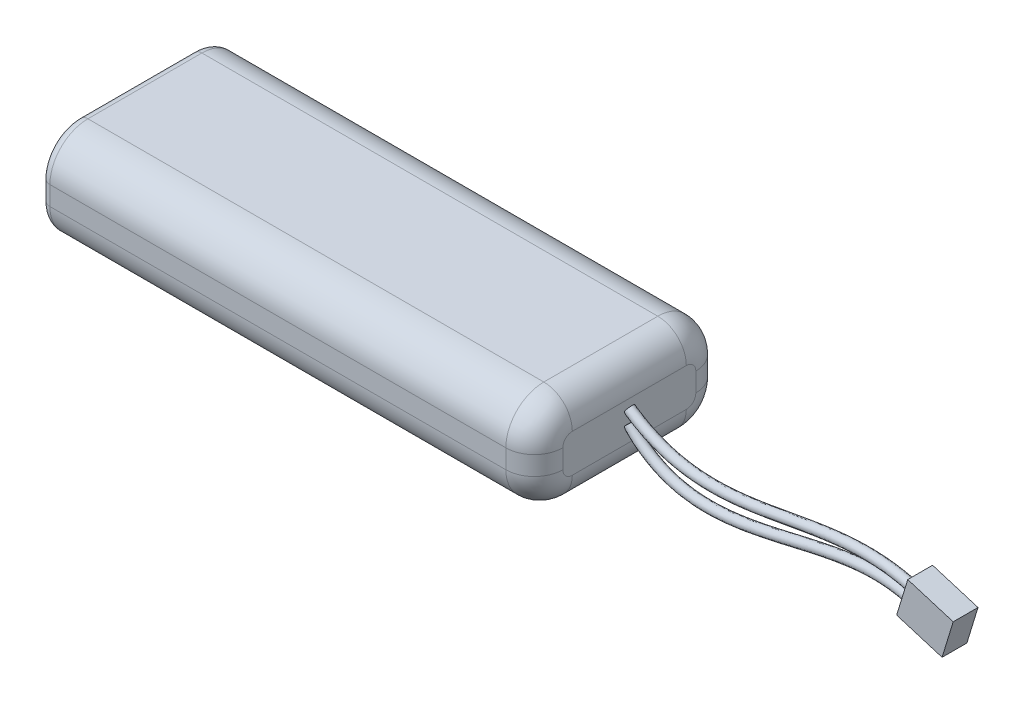
SolidWorks part; units mm, degrees
ref_plane "Front Plane" through (0, 0, 0) normal (0, 0, 1) x (1, 0, 0)
ref_plane "Top Plane" through (0, 0, 0) normal (0, 1, 0) x (1, 0, 0)
ref_plane "Right Plane" through (0, 0, 0) normal (1, 0, 0) x (0, 0, -1)
sketch "Sketch1" plane through (0, 0, 0) normal (0, 0, 1) x (1, 0, 0)
  line L1 (0, 0) -> (52, 0)
  line L2 (0, 0) -> (0, 10)
  line L3 (0, 10) -> (52, 10)
  line L4 (52, 0) -> (52, 10)
  dimension "D1" = 52
  dimension "D2" = 10
extrude "Boss-Extrude1" add sketch "Sketch1" along normal blind 20
fillet "Fillet2" radius 4 4 edges at (26, 0, 0) (26, 10, 0) (26, 0, 20) (26, 10, 20)
fillet "Fillet3" radius 3 8 edges at (52, 1.1716, 18.8284) (52, 5, 20) (52, 8.8284, 18.8284) (52, 10, 10) (52, 8.8284, 1.1716) (52, 5, 0) (52, 1.1716, 1.1716) (52, 0, 10)
ref_plane "Plane5" through (0, 0, 10) normal (0, 0, -1) x (-1, 0, 0)
sketch "Sketch6" plane through (0, 0, 10) normal (0, 0, -1) x (-1, 0, 0)
  line L1 (-52, 4) -> (-52, 6) construction
  spline S0 degree 3 poles (-52, 4.7406) (-59.6771, -3.6391) (-72.6832, 6.3221) (-81.6328, 3.5871) knots 0 0 0 0 1 1 1 1
  point P2 (-52, 10)
  point P4 (-52.2978, 12.4473)
  point P6 (0, 0)
  point P7 (0, 0)
  point P8 (0, 0)
  point P9 (0, 0)
  point P10 (-52, 10.808)
  point P13 (-52, 4.7406)
  point P14 (-57.4185, -4.9789)
  point P15 (-67.1805, -5.4193)
  point P16 (-80.6974, 6.144)
  point P17 (-67.9754, 2.4022)
  point P18 (-81.6328, 3.5871)
ref_plane "Plane6" through (81.6328, 3.5871, 10) normal (0.9563, -0.2923, 0) x (-0.2923, -0.9563, 0)
sketch "Sketch7" plane through (81.6328, 3.5871, 10) normal (0.9563, -0.2923, 0) x (-0.2923, -0.9563, 0)
  circle A0 centre (0, 0) radius 0.5
  dimension "D1" = 1
sweep "Sweep2" add profiles "Sketch7" path "Sketch6"
sketch "Sketch8" plane through (0, 0, 10) normal (0, 0, -1) x (-1, 0, 0)
  line L0 (-52, 4) -> (-52, 6) construction
  line L1 (-85.0056, 14.6239) -> (-78.26, -7.4496) construction
  spline S0 degree 3 poles (-52, 6.0909) (-61.3757, -0.4946) (-71.9516, 7.688) (-81.9749, 4.7063) knots 0 0 0 0 1 1 1 1
  point P2 (-52, 6.2503)
  point P4 (-61.1118, 2.3656)
  point P6 (0, 0)
  point P7 (-67.7091, -6.4211)
  point P12 (-66.4279, -3.9929)
  point P13 (-59.1118, 0)
  point P14 (-60.0816, -4.9142)
  point P15 (0, 0)
  point P16 (-82.3957, 6.0909)
  point P17 (-66.0634, 2.5009)
  point P18 (-69.8886, 4.6019)
  point P19 (-81.9749, 4.7063)
  point P20 (-60.2352, 3.4596)
  point P21 (-69.0578, 3.1623)
  point P22 (0, 0)
sketch "Sketch9" plane through (81.6328, 3.5871, 10) normal (0.9563, -0.2923, 0) x (-0.2923, -0.9563, 0)
  circle A0 centre (-1.1703, 0) radius 0.5
  dimension "D1" = 1
sweep "Sweep3" add profiles "Sketch9" path "Sketch8"
sketch "Sketch10" plane through (81.6328, 3.5871, 10) normal (0.9563, -0.2923, 0) x (-0.2923, -0.9563, 0)
  line L1 (-2.8259, 1.47) -> (1.1741, 1.47)
  line L2 (-2.8259, 1.47) -> (-2.8259, -1.1425)
  line L3 (-2.8259, -1.1425) -> (1.1741, -1.1425)
  line L4 (1.1741, 1.47) -> (1.1741, -1.1425)
  dimension "D1" = 4
extrude "Boss-Extrude2" add sketch "Sketch10" along normal blind 5
fillet "Fillet4" radius 1 8 edges at (0, 8.8284, 1.1716) (0, 10, 10) (0, 8.8284, 18.8284) (0, 5, 20) (0, 1.1716, 18.8284) (0, 0, 10) (0, 1.1716, 1.1716) (0, 5, 0)
